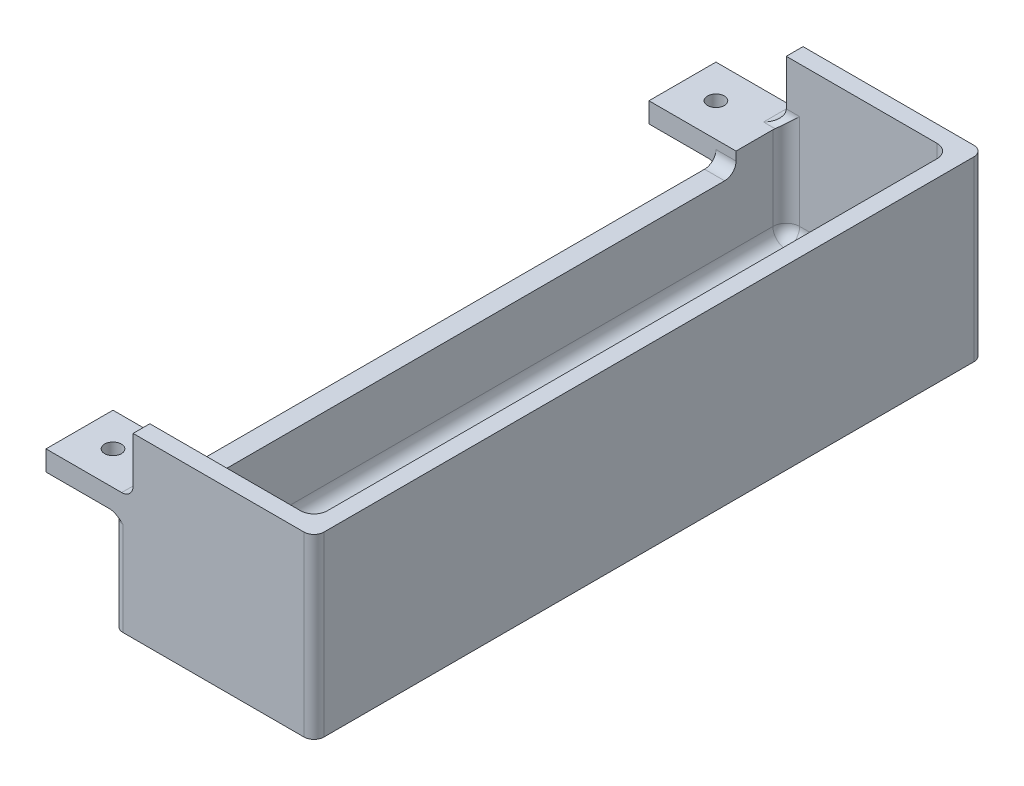
SolidWorks part; units mm, degrees
material "PLA2"
ref_plane "Front Plane" through (0, 0, 0) normal (0, 0, 1) x (1, 0, 0)
ref_plane "Top Plane" through (0, 0, 0) normal (0, 1, 0) x (1, 0, 0)
ref_plane "Right Plane" through (0, 0, 0) normal (1, 0, 0) x (0, 0, -1)
sketch " Sketch1" plane through (0, 0, 0) normal (0, 1, 0) x (1, 0, 0)
  line L0 (0, -63.5) -> (0, 63.5)
  line L1 (0, 63.5) -> (3.81, 63.5)
  line L5 (3.81, 63.5) -> (38.1, 63.5)
  line L6 (38.1, 63.5) -> (38.1, -63.5)
  line L7 (0, 0) -> (38.1, 0) construction
  line L17 (3.81, -63.5) -> (38.1, -63.5)
  line L18 (0, -63.5) -> (3.81, -63.5)
  point P3 (0, 0)
  dimension "D1" = 3.81
  dimension "D2" = 34.29
extrude "Boss-Extrude1" add sketch " Sketch1" along normal blind 4.445
sketch "Sketch2" plane through (0, 0, 0) normal (-1, 0, 0) x (0, 0, 1)
  line L0 (-63.5, 0) -> (-63.5, 19.05)
  line L1 (-63.5, 19.05) -> (63.5, 19.05)
  line L2 (63.5, 19.05) -> (63.5, 0)
  line L3 (63.5, 0) -> (-63.5, 0)
  line L5 (-63.5, 0) -> (63.5, 0) construction
  point P5 (59.3537, 0)
  point P8 (0, 0)
  dimension "D1" = 19.05
extrude "Boss-Extrude2" add sketch "Sketch2" against normal blind 3.81
sketch "Sketch3" plane through (0, 0, 63.5) normal (0, 0, 1) x (1, 0, 0)
  line L0 (3.81, 19.05) -> (-12.7, 19.05)
  line L1 (-12.7, 19.05) -> (-12.7, 22.86)
  line L2 (-12.7, 22.86) -> (3.81, 22.86)
  line L3 (3.81, 22.86) -> (3.81, 19.05)
  line L5 (0, 19.05) -> (0, 0) construction
  point P2 (0, 0)
  point P7 (0, 0)
  dimension "D1" = 12.7
  dimension "D2" = 3.81
extrude "Boss-Extrude3" add sketch "Sketch3" against normal blind 12.7
mirror "Mirror1" about plane through (0, 0, 0) normal (0, 0, 1) of "Boss-Extrude3"
sketch "Sketch4" plane through (0, 22.86, 0) normal (0, 1, 0) x (1, 0, 0)
  line L0 (-6.35, 63.5) -> (-6.35, 50.8) construction
  line L3 (0, 0) -> (38.1, 0) construction
  line L4 (38.1, -63.5) -> (38.1, 63.5) construction
  line L5 (-6.35, -63.5) -> (-6.35, -50.8) construction
  line L6 (-12.7, 50.8) -> (0, 50.8) construction
  line L7 (-12.7, 50.8) -> (0, 50.8) construction
  line L8 (3.81, 63.5) -> (-12.7, 63.5) construction
  circle A0 centre (-6.35, 57.15) radius 1.5875
  circle A1 centre (-6.35, -57.15) radius 1.5875
  dimension "D1" = 3.175
extrude "Cut-Extrude1" cut sketch "Sketch4" against normal through all
sketch "Sketch5" plane through (0, 4.445, 0) normal (0, 1, 0) x (1, 0, 0)
  line L0 (0, 0) -> (38.1, 0) construction
  line L1 (38.1, -63.5) -> (38.1, 63.5) construction
  line L2 (38.1, 1.27) -> (3.81, 1.27)
  line L3 (3.81, -50.8) -> (3.81, 50.8) construction
  line L4 (3.81, 1.27) -> (3.81, -1.27)
  line L5 (38.1, 1.27) -> (38.1, -1.27)
  line L6 (38.1, -1.27) -> (3.81, -1.27)
  point P12 (3.81, 0)
  dimension "D1" = 2.54
extrude "Divider" [suppressed] add sketch "Sketch5" along normal blind 8.89
sketch "Sketch6" plane through (0, 4.445, 0) normal (0, 1, 0) x (1, 0, 0)
  line L0 (3.81, 63.5) -> (38.1, 63.5)
  line L1 (38.1, 63.5) -> (38.1, -63.5)
  line L4 (34.925, 0) -> (34.925, 60.325)
  line L5 (34.925, 60.325) -> (3.81, 60.325)
  line L7 (3.81, 60.325) -> (3.81, 63.5)
  line L8 (0, 0) -> (38.1, 0) construction
  line L9 (0, -50.8) -> (0, 50.8) construction
  line L10 (3.81, -60.325) -> (3.81, -63.5)
  line L11 (34.925, -60.325) -> (3.81, -60.325)
  line L12 (34.925, 0) -> (34.925, -60.325)
  line L14 (3.81, -63.5) -> (38.1, -63.5)
  point P2 (0, 0)
  point P3 (0, 0)
  point P5 (0, 0)
  point P7 (0, 0)
  point P9 (0, 0)
  point P11 (34.925, -30.1625)
  point P20 (34.925, 30.1625)
  dimension "D1" = 3.175
  dimension "D2" = 3.175
extrude "Walls" add sketch "Sketch6" along normal blind 29.21
fillet "Fillet5" radius 2.54 8 edges at (3.81, 4.445, 0) (34.925, 4.445, 0) (34.925, 19.05, -60.325) (19.3675, 4.445, -60.325) (19.3675, 4.445, 60.325) (3.81, 13.6525, 60.325) (3.81, 13.6525, -60.325) (34.925, 19.05, 60.325)
fillet "Fillet7" radius 1.905 4 edges at (38.1, 16.8275, -63.5) (0, 9.525, -63.5) (38.1, 16.8275, 63.5) (0, 9.525, 63.5)
fillet "Fillet8" radius 2.159 6 edges at (5.08, 22.86, 60.325) (3.81, 22.86, 61.9125) (1.905, 19.05, 50.8) (1.905, 19.05, -50.8) (5.08, 22.86, -60.325) (3.81, 22.86, -61.9125)
fillet "Fillet9" radius 1.27 4 edges at (0.558, 19.05, 62.942) (0.558, 19.05, -62.942) (0, 19.05, 56.1975) (0, 19.05, -56.1975)
